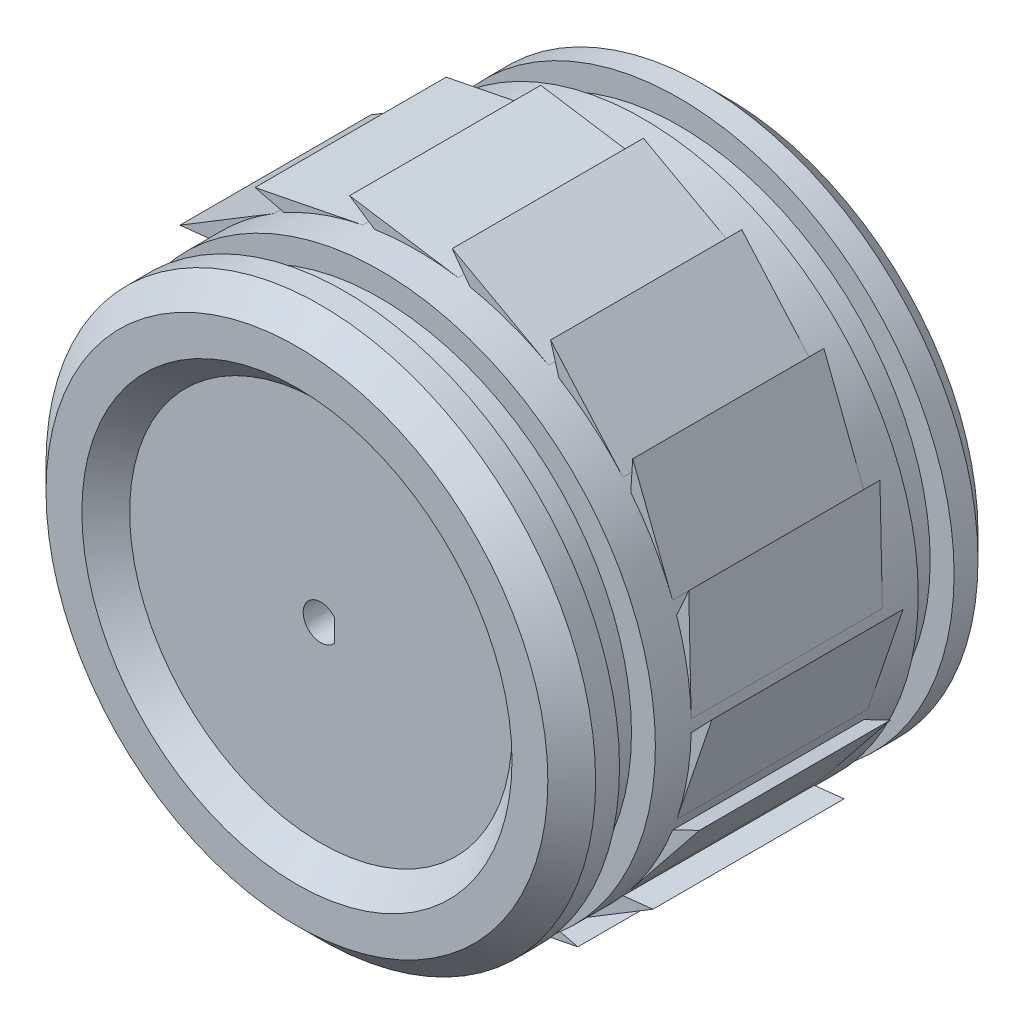
SolidWorks part; units mm, degrees
material "ABS"
ref_plane "Спереди" through (0, 0, 0) normal (0, 0, 1) x (1, 0, 0)
ref_plane "Сверху" through (0, 0, 0) normal (0, 1, 0) x (1, 0, 0)
ref_plane "Справа" through (0, 0, 0) normal (1, 0, 0) x (0, 0, -1)
sketch "Эскиз1" plane through (0, 0, 0) normal (1, 0, 0) x (0, 0, -1)
  line L0 (0, 22.5472) -> (0, -23.5635) construction
  line L1 (0, 23) -> (-16, 23)
  line L2 (-18, 21) -> (-18, 18)
  line L5 (-16, 16) -> (-16, 0)
  line L9 (16, 23) -> (0, 23)
  line L10 (-28.6739, 0) -> (34.4859, 0) construction
  line L11 (-18, 18) -> (-16, 16)
  line L12 (18, 21) -> (16, 23)
  line L14 (-16, 0) -> (-14.3343, 0)
  line L15 (-12, 10) -> (-12, 13.5)
  line L16 (-8, 17.5) -> (18, 17.5)
  line L17 (18, 17.5) -> (18, 21)
  line L19 (-16, 23) -> (-18, 21)
  line L20 (-12, 13.5) -> (-8, 17.5)
  line L21 (-16, 16) -> (-18, 16) construction
  line L22 (-14.3343, 0) -> (-6, 0)
  line L25 (-6, 0) -> (-6, 4)
  line L26 (-18, 16) -> (-18, 23) construction
  line L27 (-18, 23) -> (-16, 23) construction
  line L28 (16, 23) -> (18, 23) construction
  line L29 (18, 23) -> (18, 21) construction
  spline S0 degree 3 poles (-12, 10) (-11.4864, 10) (-7.5212, 9.1569) (-6, 5.0213) (-6, 4) knots 0 0 0 0 0.351629 1 1 1 1
  point P4 (-18, 23)
  point P6 (-18, 16)
  point P10 (-12, 17.5)
  point P11 (18, 23)
  dimension "D1" = 35
  dimension "D2" = 4
  dimension "D4" = 20
  dimension "D5" = 6
  dimension "D9" = 3
  dimension "D8" = 36
  dimension "D11" = 46
  dimension "D12" = 18
  dimension "D13" = 7
  dimension "D14" = 8
ref_axis "Ось1" through (0, 0, -80.9) along (0, 0, 1)
revolve "Повернуть1" add sketch "Эскиз1" angle 360 about L10 region at (0, 22.5728, -8)
sketch "Эскиз2" plane through (0, 0, 16) normal (0, 0, 1) x (1, 0, 0)
  line L0 (1.125, 0.9539) -> (1.125, -0.9539)
  circle A0 centre (0, 0) radius 1.475
  point P5 (-1.475, 0)
  dimension "D1" = 2.95
  dimension "D2" = 2.6
extrude "Вырез-Вытянуть1" cut sketch "Эскиз2" against normal through all contours L0 A0 region at (-0.0907, 0, 16)
ref_plane "Плоскость1" through (0, 20, 0) normal (0, 1, 0) x (1, 0, 0)
sketch "Эскиз3" plane through (0, 0, 0) normal (1, 0, 0) x (0, 0, -1)
  line L0 (-27.6376, 0) -> (18.0085, 0) construction
  line L1 (18, 21) -> (16, 23)
  line L2 (16, 23) -> (14, 23)
  line L3 (16, 23) -> (-16, 23) construction
  line L4 (14, 23) -> (14, 21)
  line L5 (14, 21) -> (11, 21)
  line L6 (11, 21) -> (11, 23)
  line L7 (11, 23) -> (-11, 23)
  line L8 (-11, 23) -> (-11, 21)
  line L9 (-11, 21) -> (-14, 21)
  line L10 (-14, 21) -> (-14, 23)
  line L11 (-14, 23) -> (-16, 23)
  line L12 (-16, 23) -> (-18, 21)
  line L13 (-18, 21) -> (-18, 24.3347)
  line L14 (-18, 24.3347) -> (18, 24.3347)
  line L15 (18, 24.3347) -> (18, 21)
  dimension "D1" = 2
  dimension "D2" = 2
  dimension "D3" = 3
  dimension "D4" = 3
  dimension "D5" = 2
revolve "Вырез-Повернуть1" cut sketch "Эскиз3" angle 360 about L0
sketch "Эскиз4" plane through (0, 0, 0) normal (0, 0, 1) x (1, 0, 0)
  line L0 (0, 25.4704) -> (0, -25.2707) construction
  line L1 (-3.5, 22.7321) -> (-5.5929, 24.1321)
  line L2 (-5.5929, 24.1321) -> (3.5, 22.7321)
  line L3 (2.9981, 24.5897) -> (11.0638, 20.1641)
  line L4 (4.4859, 22.5583) -> (2.9981, 24.5897)
  line L5 (11.2275, 22.0813) -> (17.2931, 15.1641)
  line L6 (11.9308, 19.6636) -> (11.2275, 22.0813)
  line L7 (18.1026, 16.9096) -> (21.4366, 8.335)
  line L8 (17.9366, 14.3972) -> (18.1026, 16.9096)
  line L9 (22.7943, 9.6984) -> (22.9946, 0.5006)
  line L10 (21.779, 7.3942) -> (22.7943, 9.6984)
  line L11 (24.7367, 1.3174) -> (21.779, -7.3942)
  line L12 (22.9946, -0.5006) -> (24.7367, 1.3174)
  line L13 (23.6955, -7.2225) -> (17.9366, -14.3972)
  line L14 (21.4366, -8.335) -> (23.6955, -7.2225)
  line L15 (19.7962, -14.8913) -> (11.9308, -19.6636)
  line L16 (17.2931, -15.1641) -> (19.7962, -14.8913)
  line L17 (13.5092, -20.7639) -> (4.4859, -22.5583)
  line L18 (11.0638, -20.1641) -> (13.5092, -20.7639)
  line L19 (5.5929, -24.1321) -> (-3.5, -22.7321)
  line L20 (3.5, -22.7321) -> (5.5929, -24.1321)
  line L21 (-2.9981, -24.5897) -> (-11.0638, -20.1641)
  line L22 (-4.4859, -22.5583) -> (-2.9981, -24.5897)
  line L23 (-11.2275, -22.0813) -> (-17.2931, -15.1641)
  line L24 (-11.9308, -19.6636) -> (-11.2275, -22.0813)
  line L25 (-18.1026, -16.9096) -> (-21.4366, -8.335)
  line L26 (-17.9366, -14.3972) -> (-18.1026, -16.9096)
  line L27 (-22.7943, -9.6984) -> (-22.9946, -0.5006)
  line L28 (-21.779, -7.3942) -> (-22.7943, -9.6984)
  line L29 (-24.7367, -1.3174) -> (-21.779, 7.3942)
  line L30 (-22.9946, 0.5006) -> (-24.7367, -1.3174)
  line L31 (-23.6955, 7.2225) -> (-17.9366, 14.3972)
  line L32 (-21.4366, 8.335) -> (-23.6955, 7.2225)
  line L33 (-19.7962, 14.8913) -> (-11.9308, 19.6636)
  line L34 (-17.2931, 15.1641) -> (-19.7962, 14.8913)
  line L35 (-13.5092, 20.7639) -> (-4.4859, 22.5583)
  line L36 (-11.0638, 20.1641) -> (-13.5092, 20.7639)
  arc A0 (3.5, 22.7321) -> (-3.5, 22.7321) centre (0, 0) ccw
  arc A1 (11.0638, 20.1641) -> (4.4859, 22.5583) centre (0, 0) ccw
  circle A2 centre (0, 0) radius 23 construction
  arc A3 (17.2931, 15.1641) -> (11.9308, 19.6636) centre (0, 0) ccw
  arc A4 (21.4366, 8.335) -> (17.9366, 14.3972) centre (0, 0) ccw
  arc A5 (22.9946, 0.5006) -> (21.779, 7.3942) centre (0, 0) ccw
  arc A6 (21.779, -7.3942) -> (22.9946, -0.5006) centre (0, 0) ccw
  arc A7 (17.9366, -14.3972) -> (21.4366, -8.335) centre (0, 0) ccw
  arc A8 (11.9308, -19.6636) -> (17.2931, -15.1641) centre (0, 0) ccw
  arc A9 (4.4859, -22.5583) -> (11.0638, -20.1641) centre (0, 0) ccw
  arc A10 (-3.5, -22.7321) -> (3.5, -22.7321) centre (0, 0) ccw
  arc A11 (-11.0638, -20.1641) -> (-4.4859, -22.5583) centre (0, 0) ccw
  arc A12 (-17.2931, -15.1641) -> (-11.9308, -19.6636) centre (0, 0) ccw
  arc A13 (-21.4366, -8.335) -> (-17.9366, -14.3972) centre (0, 0) ccw
  arc A14 (-22.9946, -0.5006) -> (-21.779, -7.3942) centre (0, 0) ccw
  arc A15 (-21.779, 7.3942) -> (-22.9946, 0.5006) centre (0, 0) ccw
  arc A16 (-17.9366, 14.3972) -> (-21.4366, 8.335) centre (0, 0) ccw
  arc A17 (-11.9308, 19.6636) -> (-17.2931, 15.1641) centre (0, 0) ccw
  arc A18 (-4.4859, 22.5583) -> (-11.0638, 20.1641) centre (0, 0) ccw
  point P63 (0, 0)
  dimension "D1" = 7
  dimension "D2" = 1.4
  dimension "D3" = 18
extrude "Бобышка-Вытянуть1" add sketch "Эскиз4" along normal mid plane 16
equation "\"D2@Эскиз3\"=\"D1@Эскиз3\""
equation "\"D4@Эскиз3\"=\"D3@Эскиз3\""
